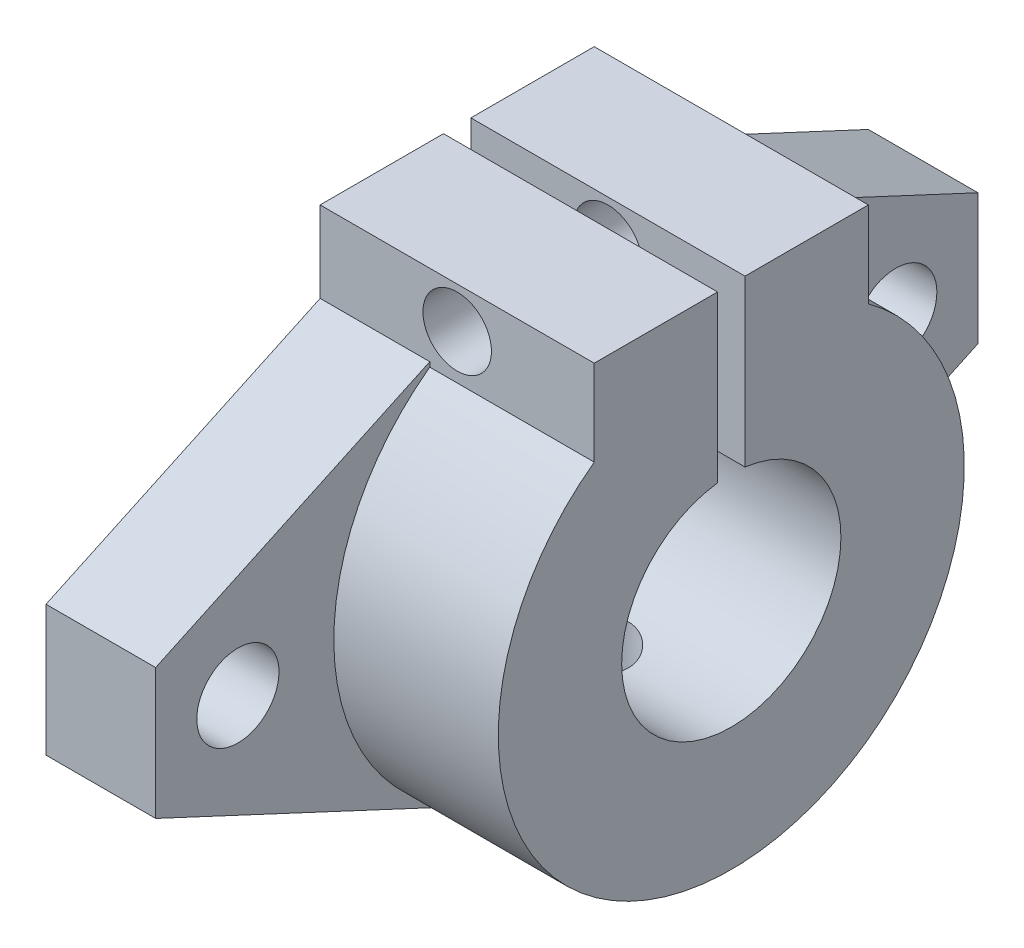
SolidWorks part; units mm, degrees
material "6061 合金"
ref_plane "前视基准面" through (0, 0, 0) normal (0, 0, 1) x (1, 0, 0)
ref_plane "上视基准面" through (0, 0, 0) normal (0, 1, 0) x (1, 0, 0)
ref_plane "右视基准面" through (0, 0, 0) normal (1, 0, 0) x (0, 0, -1)
sketch "草图1" plane through (0, 0, 0) normal (1, 0, 0) x (0, 0, -1)
  line L0 (-51.8991, 0) -> (49.8448, 0) construction
  line L1 (0, 31.9917) -> (0, -30.8598) construction
  line L2 (-30, 4.7682) -> (-30, -4.7682)
  line L3 (-7.1845, 15.4072) -> (-30, 4.7682)
  line L4 (-7.1845, -15.4072) -> (-30, -4.7682)
  line L5 (7.1845, -15.4072) -> (30, -4.7682)
  line L6 (30, 4.7682) -> (30, -4.7682)
  line L7 (7.1845, 15.4072) -> (30, 4.7682)
  circle A0 centre (0, 0) radius 17
  circle A1 centre (0, 0) radius 8
  circle A2 centre (-24, 0) radius 3
  circle A3 centre (24, 0) radius 3
  dimension "D1" = 16
  dimension "D2" = 34
  dimension "D3" = 48
  dimension "D4" = 6
  dimension "D5" = 60
  dimension "D6" = 115
extrude "凸台-拉伸1" add sketch "草图1" along normal blind 8 contours A0 L3 L2 L4 A2 | A0 L5 L6 L7 A3 region at (0, 9.7402, 18.4302) region at (0, 9.7402, -18.4302)
extrude "凸台-拉伸2" add sketch "草图1<3>" along normal blind 20 contours A0 A1 region at (0, 16.5192, 0)
sketch "草图1<3>" plane through (0, 0, 0) normal (1, 0, 0) x (0, 0, -1) same geometry as "草图1"
ref_plane "基准面1" through (0, 20, 0) normal (0, 1, 0) x (1, 0, 0)
sketch "草图2" plane through (0, 20, 0) normal (0, 1, 0) x (1, 0, 0)
  line L0 (0, 0) -> (20, 0) construction
  line L1 (20, -17) -> (20, 17) construction
  line L3 (0, -10) -> (20, -10)
  line L4 (0, -10) -> (0, 10)
  line L5 (0, 10) -> (20, 10)
  line L6 (20, -10) -> (20, 10)
  line L7 (0, -10) -> (20, 10) construction
  line L8 (0, 10) -> (20, -10) construction
  point P5 (10, 0)
  dimension "D1" = 20
extrude "凸台-拉伸3" add sketch "草图2" against normal up to next contours L5 L6 L3 L4
sketch "草图3" plane through (0, 20, 0) normal (0, 1, 0) x (1, 0, 0)
  line L0 (0, 0) -> (20, 0) construction
  line L1 (20, -10) -> (20, 10) construction
  line L3 (0, -1) -> (20, -1)
  line L4 (0, -1) -> (0, 1)
  line L5 (0, 1) -> (20, 1)
  line L6 (20, -1) -> (20, 1)
  line L7 (0, -1) -> (20, 1) construction
  line L8 (0, 1) -> (20, -1) construction
  point P5 (10, 0)
  dimension "D1" = 2
extrude "切除-拉伸1" cut sketch "草图3" against normal blind 20
sketch "草图4" plane through (0, 0, 10) normal (0, 0, 1) x (1, 0, 0)
  line L0 (0, 18.6834) -> (20, 18.6834) construction
  line L1 (0, 14.0943) -> (0, 20) construction
  line L2 (20, 13.7477) -> (20, 20) construction
  line L3 (10, 18.6834) -> (10, 15.3166) construction
  line L4 (11, 20) -> (-11, 20) construction
  circle A0 centre (10, 17) radius 2.5
  dimension "D1" = 5
  dimension "D2" = 3
extrude "切除-拉伸2" cut sketch "草图4" against normal through all contours A0
sketch "草图5" plane through (0, 0, 0) normal (0, 1, 0) x (1, 0, 0)
  line L0 (0, 1) -> (0, 10) construction
  circle A0 centre (10, 0) radius 2.5
  dimension "D1" = 5
  dimension "D2" = 10
extrude "切除-拉伸3" cut sketch "草图5" against normal through all
